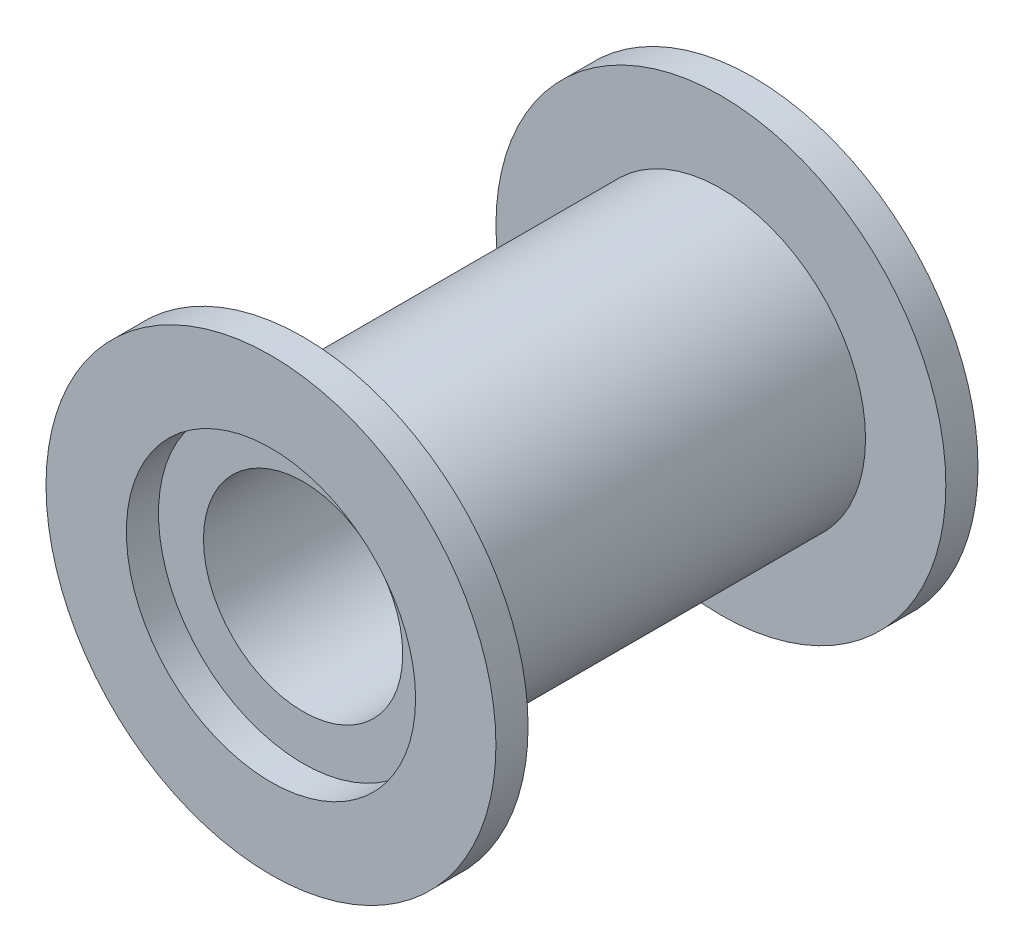
SolidWorks part; units mm, degrees
ref_plane "Спереди" through (0, 0, 0) normal (0, 0, 1) x (1, 0, 0)
ref_plane "Сверху" through (0, 0, 0) normal (0, 1, 0) x (1, 0, 0)
ref_plane "Справа" through (0, 0, 0) normal (1, 0, 0) x (0, 0, -1)
sketch "Эскиз1" plane through (0, 0, 0) normal (0, 0, 1) x (1, 0, 0)
  circle A0 centre (0, 0) radius 3.1
  circle A1 centre (0, 0) radius 7
  circle A2 centre (0, 0) radius 4.5
extrude "Бобышка-Вытянуть2" add sketch "Эскиз1" along normal blind 14 contours A2 A0 region at (-4.3727, 0, 0)
extrude "Бобышка-Вытянуть3" add sketch "Эскиз1<4>" along normal blind 1 contours A1 A2 region at (-6.802, 0, 0)
sketch "Эскиз1<4>" plane through (0, 0, 0) normal (0, 0, 1) x (1, 0, 0) same geometry as "Эскиз1"
sketch "Эскиз2" plane through (0, 0, 14) normal (0, 0, 1) x (1, 0, 0)
  circle A0 centre (0, 0) radius 7
  circle A1 centre (0, 0) radius 4.5
extrude "Бобышка-Вытянуть4" add sketch "Эскиз2" along normal blind 1 separate body
